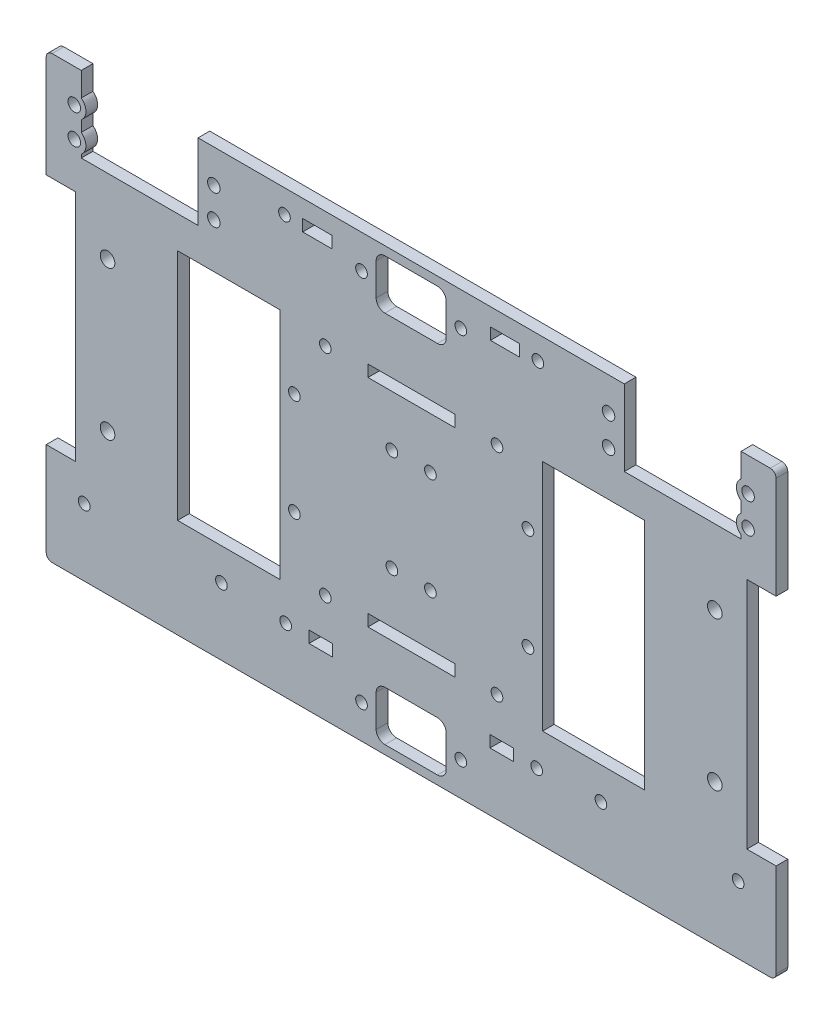
SolidWorks part; units mm, degrees
ref_plane "Front Plane" through (0, 0, 0) normal (0, 0, 1) x (1, 0, 0)
ref_plane "Top Plane" through (0, 0, 0) normal (0, 1, 0) x (1, 0, 0)
ref_plane "Right Plane" through (0, 0, 0) normal (1, 0, 0) x (0, 0, -1)
sketch "Sketch1" plane through (0, 0, 0) normal (0, 0, 1) x (1, 0, 0)
  line L1 (-123, 77) -> (123, 77)
  line L2 (-125, 75) -> (-125, -72)
  line L3 (-123, -74) -> (123, -74)
  line L4 (125, 75) -> (125, -72)
  arc A0 (123, 77) -> (125, 75) centre (123, 75) cw
  arc A1 (-125, 75) -> (-123, 77) centre (-123, 75) cw
  arc A2 (125, -72) -> (123, -74) centre (123, -72) cw
  arc A3 (-125, -72) -> (-123, -74) centre (-123, -72) ccw
  point P7 (125, 77)
  point P10 (-125, 77)
  point P15 (-125, -74)
  dimension "D5" = 2
  dimension "D6" = 2
  dimension "D7" = 2
  dimension "D1" = 250
  dimension "D2" = 151
  dimension "D3" = 74
  dimension "D4" = 125
extrude "Boss-Extrude1" add sketch "Sketch1" along normal blind 4
sketch "Sketch2" plane through (0, 0, 0) normal (0, 0, -1) x (-1, 0, 0)
  line L0 (0, 77) -> (0, -74) construction
  line L4 (-123, 77) -> (123, 77) construction
  line L5 (123, -74) -> (-123, -74) construction
  line L10 (-125, 40) -> (-125, -40)
  line L15 (-115, -40) -> (-125, -40)
  line L16 (-115, 40) -> (-115, -40)
  line L17 (-125, 40) -> (-115, 40)
  line L18 (-45, -40) -> (-80, -40)
  line L19 (-80, -40) -> (-80, 40)
  line L20 (-80, 40) -> (-45, 40)
  line L21 (-45, 40) -> (-45, -40)
  line L22 (125, 40) -> (115, 40)
  line L23 (-125, -72) -> (-125, 75) construction
  line L24 (-192.8803, 0) -> (128.2258, 0) construction
  line L25 (115, 40) -> (115, -40)
  line L26 (115, -40) -> (125, -40)
  line L27 (125, 40) -> (125, -40)
  line L28 (45, 40) -> (45, -40)
  line L29 (80, 40) -> (45, 40)
  line L30 (80, -40) -> (80, 40)
  line L31 (45, -40) -> (80, -40)
  circle A4 centre (-6.6, -17.5) radius 2
  circle A5 centre (-6.6, 17.5) radius 2
  circle A6 centre (-40, -17.5) radius 2
  circle A7 centre (-40, 17.5) radius 2
  circle A8 centre (6.6, 17.5) radius 2
  circle A9 centre (6.6, -17.5) radius 2
  circle A10 centre (40, -17.5) radius 2
  circle A11 centre (40, 17.5) radius 2
  point P24 (-80, 0)
  dimension "D14" = 4
  dimension "D15" = 4
  dimension "D16" = 4
  dimension "D17" = 4
  dimension "D18" = 115
  dimension "D19" = 40
  dimension "D2" = 40
  dimension "D3" = 45
  dimension "D4" = 10
  dimension "D5" = 45
  dimension "D6" = 40
  dimension "D7" = 17.5
  dimension "D8" = 40
  dimension "D9" = 40
  dimension "D10" = 40
  dimension "D11" = 33.4
  dimension "D12" = 33.4
  dimension "D13" = 35
extrude "Cut-Extrude1" cut sketch "Sketch2" against normal blind 10
sketch "Sketch4" plane through (0, 0, 0) normal (0, 0, -1) x (-1, 0, 0)
  line L5 (15, 35) -> (15, 40.2)
  line L7 (-15, 35) -> (-15, 40.2)
  line L9 (-15, -40.2) -> (15, -40.2)
  line L14 (0, 0) -> (-74.7246, 0) construction
  line L15 (15, -35) -> (-15, -35)
  line L16 (0, 0) -> (0, 45.381) construction
  line L20 (15, 35) -> (15, 40.2)
  line L21 (-15, -35) -> (-15, -40.2)
  line L22 (15, -35) -> (15, -40.2)
  line L23 (-15, -35) -> (-15, -40.2)
  line L24 (15, -35) -> (15, -40.2)
  line L25 (-15, 35) -> (-15, 40.2)
  line L26 (15, 35) -> (-15, 35)
  line L27 (-15, 40.2) -> (15, 40.2)
  line L28 (-45, -40) -> (-45, 40) construction
  dimension "D1" = 30
  dimension "D2" = 35
  dimension "D3" = 5.2
  dimension "D4" = 30
extrude "Cut-Extrude3" [suppressed] cut sketch "Sketch4" against normal blind 10 contours L22 L15 L21 L9 | L27 L7 L26 L5
sketch "Sketch6" plane through (0, 0, 0) normal (0, 0, -1) x (-1, 0, 0)
  line L0 (0, 0) -> (-136.3879, 0) construction
  line L1 (0, 0) -> (0, 55.1301) construction
  circle A1 centre (-104, -25.5) radius 2.5
  circle A3 centre (-104, 25.5) radius 2.5
  circle A4 centre (104, -25.5) radius 2.5
  circle A5 centre (104, 25.5) radius 2.5
  dimension "D1" = 5
  dimension "D2" = 5
  dimension "D3" = 25.5
  dimension "D4" = 104
  dimension "D5" = 51
extrude "Cut-Extrude5" cut sketch "Sketch6" against normal blind 10
sketch "Sketch7" plane through (0, 0, 0) normal (0, 0, -1) x (-1, 0, 0)
  line L0 (0, 0) -> (0, -64.9277) construction
  line L1 (0, 0) -> (-69.7221, 0) construction
  circle A0 centre (29.9, 37.5) radius 2
  circle A1 centre (-29.9, -37.5) radius 2
  circle A2 centre (-29.9, 37.5) radius 2
  circle A3 centre (29.9, -37.5) radius 2
  dimension "D3" = 4
  dimension "D5" = 4
  dimension "D1" = 29.9
  dimension "D2" = 37.5
  dimension "D4" = 59.8
extrude "Cut-Extrude6" [suppressed] cut sketch "Sketch7" against normal blind 10 contours A1 | A3 | A2 | A0
sketch "Sketch8" plane through (0, 0, 0) normal (0, 0, -1) x (-1, 0, 0)
  line L0 (0, 0) -> (0, 89.5315) construction
  line L1 (0, 0) -> (69.2283, 0) construction
  line L2 (5.5, 71) -> (-5.5, 71)
  line L3 (-8.5, 68) -> (-8.5, 53)
  line L4 (-5.5, 50) -> (5.5, 50)
  line L5 (8.5, 53) -> (8.5, 68)
  line L6 (-123, 77) -> (123, 77) construction
  arc A0 (-8.5, 68) -> (-5.5, 71) centre (-5.5, 68) cw
  arc A1 (-8.5, 53) -> (-5.5, 50) centre (-5.5, 53) ccw
  arc A2 (5.5, 50) -> (8.5, 53) centre (5.5, 53) ccw
  arc A3 (5.5, 71) -> (8.5, 68) centre (5.5, 68) cw
  dimension "D5" = 3
  dimension "D1" = 6
  dimension "D2" = 8.5
  dimension "D3" = 8.5
  dimension "D4" = 21
extrude "Cut-Extrude7" [suppressed] cut sketch "Sketch8" against normal blind 70
sketch "Sketch10" plane through (0, 0, 0) normal (0, 0, -1) x (-1, 0, 0)
  line L0 (0, 0) -> (59.5887, 0) construction
  line L1 (0, 0) -> (0, 43.3786) construction
  circle A0 centre (13, 60.5) radius 2
  circle A1 centre (-13, 60.5) radius 2
  dimension "D2" = 4
  dimension "D3" = 4
  dimension "D1" = 13
  dimension "D4" = 13
  dimension "D5" = 60.5
extrude "Cut-Extrude8" [suppressed] cut sketch "Sketch10" against normal blind 5
sketch "Sketch11" plane through (0, 0, 0) normal (0, 0, -1) x (-1, 0, 0)
  line L0 (0, 0) -> (0, -54) construction
  line L1 (0, 0) -> (-72.0295, 0) construction
  line L2 (123, -74) -> (-123, -74) construction
  line L3 (-9, -54) -> (9, -54)
  line L4 (-12, -57) -> (-12, -68)
  line L5 (-9, -71) -> (9, -71)
  line L6 (12, -57) -> (12, -68)
  line L8 (-9, 74) -> (9, 74)
  line L9 (-12, 60) -> (-12, 71)
  line L10 (-9, 57) -> (9, 57)
  line L11 (0, 74) -> (0, 57) construction
  line L13 (-123, 77) -> (123, 77) construction
  line L14 (12, 60) -> (12, 71)
  arc A0 (12, -68) -> (9, -71) centre (9, -68) cw
  arc A1 (12, -57) -> (9, -54) centre (9, -57) ccw
  arc A2 (-12, -68) -> (-9, -71) centre (-9, -68) ccw
  arc A3 (-12, -57) -> (-9, -54) centre (-9, -57) cw
  circle A4 centre (-17, -62.5) radius 2
  circle A5 centre (17, -62.5) radius 2
  circle A7 centre (-17, 65.5) radius 2
  arc A8 (-12, 60) -> (-9, 57) centre (-9, 60) ccw
  arc A9 (-12, 71) -> (-9, 74) centre (-9, 71) cw
  arc A10 (12, 71) -> (9, 74) centre (9, 71) ccw
  arc A11 (12, 60) -> (9, 57) centre (9, 60) cw
  circle A12 centre (17, 65.5) radius 2
  dimension "D5" = 3
  dimension "D7" = 4
  dimension "D10" = 4
  dimension "D13" = 3
  dimension "D14" = 3
  dimension "D15" = 9
  dimension "D17" = 3
  dimension "D20" = 4
  dimension "D1" = 12
  dimension "D2" = 12
  dimension "D3" = 17
  dimension "D4" = 20
  dimension "D6" = 11.5
  dimension "D8" = 17
  dimension "D9" = 17
  dimension "D11" = 9
  dimension "D12" = 11
  dimension "D16" = 17
  dimension "D19" = 5.5
  dimension "D24" = 5
extrude "Cut-Extrude9" cut sketch "Sketch11" against normal blind 10
sketch "Sketch16" plane through (0, 0, 0) normal (0, 0, -1) x (-1, 0, 0)
  line L0 (-113, 77) -> (-113, 51)
  line L1 (-123, 77) -> (123, 77) construction
  line L2 (-113, 51) -> (-73, 51)
  line L3 (-73, 51) -> (-73, 77)
  line L5 (0, 0) -> (0, 95.5672) construction
  line L6 (0, 0) -> (-125.0994, 0) construction
  line L7 (-113, 77) -> (-73, 77)
  line L8 (113, 77) -> (73, 77)
  line L9 (73, 51) -> (73, 77)
  line L10 (113, 51) -> (73, 51)
  line L11 (113, 77) -> (113, 51)
  dimension "D1" = 73
  dimension "D3" = 40
  dimension "D4" = 26
extrude "Cut-Extrude10" cut sketch "Sketch16" against normal blind 10
sketch "Sketch17" plane through (0, 0, 0) normal (0, 0, -1) x (-1, 0, 0)
  line L0 (0, 0) -> (-153.5219, 0) construction
  line L1 (0, 0) -> (0, 113.679) construction
  circle A1 centre (67.6, 65.6) radius 2.15
  circle A3 centre (67.6, 55.4) radius 2.15
  circle A5 centre (115.4, 55.4) radius 2.15
  circle A7 centre (115.4, 65.6) radius 2.15
  circle A8 centre (-115.4, 65.6) radius 2.15
  circle A9 centre (-115.4, 55.4) radius 2.15
  circle A10 centre (-67.6, 55.4) radius 2.15
  circle A11 centre (-67.6, 65.6) radius 2.15
  dimension "D1" = 4.3
  dimension "D2" = 4.3
  dimension "D3" = 4.3
  dimension "D4" = 4.3
  dimension "D5" = 65.6
  dimension "D6" = 115.4
  dimension "D7" = 10.2
  dimension "D8" = 47.8
extrude "Cut-Extrude11" cut sketch "Sketch17" against normal blind 10
sketch "Sketch18" plane through (0, 0, 0) normal (0, 0, -1) x (-1, 0, 0)
  line L0 (-73, 77) -> (73, 77) construction
  line L2 (73, 77) -> (73, 51) construction
  line L3 (-73, 51) -> (-73, 77) construction
  circle A0 centre (-43.2, 68.5) radius 2
  circle A2 centre (43.2, 68.5) radius 2
  dimension "D1" = 4
  dimension "D2" = 68.5
  dimension "D3" = 4
  dimension "D4" = 8.5
  dimension "D5" = 29.8
  dimension "D6" = 29.8
extrude "Cut-Extrude12" [suppressed] cut sketch "Sketch18" against normal blind 10
sketch "Sketch19" plane through (0, 0, 0) normal (0, 0, -1) x (-1, 0, 0)
  line L0 (123, -74) -> (-123, -74) construction
  line L1 (0, 0) -> (0, -74) construction
  line L22 (-73, 51) -> (-113, 51)
  line L23 (-73, 77) -> (-73, 51)
  line L24 (73, 77) -> (-73, 77)
  line L25 (73, 51) -> (73, 77)
  line L26 (113, 51) -> (73, 51)
  line L27 (113, 77) -> (113, 51)
  line L28 (123, 77) -> (113, 77)
  line L29 (125, 40) -> (125, 75)
  line L30 (115, 40) -> (125, 40)
  line L31 (115, -40) -> (115, 40)
  line L32 (125, -40) -> (115, -40)
  line L33 (125, -72) -> (125, -40)
  line L34 (-123, -74) -> (123, -74)
  line L35 (-125, -40) -> (-125, -72)
  line L36 (-115, -40) -> (-125, -40)
  line L37 (-115, 40) -> (-115, -40)
  line L38 (-125, 40) -> (-115, 40)
  line L39 (125, -72) -> (125, -40)
  line L40 (-113, 77) -> (-123, 77)
  line L41 (-113, 51) -> (-113, 77)
  line L52 (125, -40) -> (115, -40)
  line L54 (-123, -74) -> (123, -74)
  line L55 (-125, -40) -> (-125, -72)
  line L56 (-115, -40) -> (-125, -40)
  line L57 (-125, 75) -> (-125, 40)
  arc A4 (125, 75) -> (123, 77) centre (123, 75) ccw
  arc A5 (123, -74) -> (125, -72) centre (123, -72) ccw
  arc A6 (-125, -72) -> (-123, -74) centre (-123, -72) ccw
  arc A7 (-123, 77) -> (-125, 75) centre (-123, 75) ccw
  arc A9 (123, -74) -> (125, -72) centre (123, -72) ccw
  arc A10 (-125, -72) -> (-123, -74) centre (-123, -72) ccw
  spline S0 degree 2 poles (-115, -40) (-63.7221, -74) (0, -74) knots 0 0 0 1 1 1
  spline S1 degree 2 poles (115, -40) (63.7221, -74) (0, -74) knots 0 0 0 1 1 1
  point P5 (0, -74)
  dimension "D1" = 0
extrude "Cut-Extrude14" [suppressed] cut sketch "Sketch19" against normal blind 5 contours L52 S1 L54 A9 L39 | S0 L56 L55 A10 L54
sketch "Sketch24" plane through (0, 0, 0) normal (0, 0, -1) x (-1, 0, 0)
  line L5 (0, 0) -> (-23.4044, 0) construction
  line L12 (0, 0) -> (0, -63.755) construction
  circle A0 centre (-42.8, -52.5) radius 2
  circle A2 centre (42.8, -52.5) radius 2
  dimension "D1" = 4
  dimension "D2" = 42.8
  dimension "D3" = 52.5
extrude "Cut-Extrude17" [suppressed] cut sketch "Sketch24" against normal blind 5
sketch "Sketch26" plane through (0, 0, 0) normal (0, 0, -1) x (-1, 0, 0)
  line L0 (0, 0) -> (0, -87.1196) construction
  line L1 (0, 0) -> (-65, 0) construction
  circle A1 centre (-112, -51) radius 2
  circle A3 centre (-65, -51) radius 2
  circle A4 centre (65, -51) radius 2
  circle A5 centre (112, -51) radius 2
  dimension "D2" = 65
  dimension "D3" = 4
  dimension "D4" = 4
  dimension "D1" = 51
  dimension "D5" = 47
extrude "Cut-Extrude18" cut sketch "Sketch26" against normal blind 10
sketch "Sketch28" plane through (0, 0, 0) normal (0, 0, -1) x (-1, 0, 0)
  line L0 (0, 0) -> (0, 91.6279) construction
  circle A0 centre (-115.4, 65.6) radius 2.15
  circle A1 centre (-115.4, 65.6) radius 4
  circle A2 centre (-115.4, 55.4) radius 2.15
  circle A3 centre (-115.4, 55.4) radius 4
  circle A4 centre (115.4, 55.4) radius 4
  circle A5 centre (115.4, 55.4) radius 2.15
  circle A6 centre (115.4, 65.6) radius 4
  circle A7 centre (115.4, 65.6) radius 2.15
  dimension "D1" = 4.3
  dimension "D2" = 8
  dimension "D3" = 4.3
  dimension "D4" = 8
extrude "Boss-Extrude2" add sketch "Sketch28" against normal blind 4
sketch "Sketch29" plane through (0, 0, 4) normal (0, 0, 1) x (1, 0, 0)
  line L24 (-27, -50) -> (-27, -54)
  line L25 (-27, -54) -> (-35, -54)
  line L26 (-35, -50) -> (-35, -54)
  line L27 (-27, -50) -> (-35, -50)
  line L28 (35, -50) -> (35, -54)
  line L29 (35, -54) -> (27, -54)
  line L30 (27, -50) -> (27, -54)
  line L31 (35, -50) -> (27, -50)
  line L32 (15, -35) -> (15, -39)
  line L33 (15, -39) -> (-14.8, -39)
  line L34 (-14.8, -35) -> (-14.8, -39)
  line L35 (15, -35) -> (-14.8, -35)
  line L36 (15, 39) -> (15, 35)
  line L37 (15, 35) -> (-14.8, 35)
  line L38 (-14.8, 39) -> (-14.8, 35)
  line L39 (15, 39) -> (-14.8, 39)
  line L40 (27.15, 71) -> (37.15, 71)
  line L41 (37.15, 67) -> (37.15, 71)
  line L42 (27.15, 67) -> (37.15, 67)
  line L43 (27.15, 67) -> (27.15, 71)
  line L44 (-37.15, 67) -> (-37.15, 71)
  line L45 (-37.15, 67) -> (-27.15, 67)
  line L46 (-27.15, 67) -> (-27.15, 71)
  line L47 (-37.15, 71) -> (-27.15, 71)
extrude "Cut-Extrude19" cut sketch "Sketch29" against normal blind 10
sketch "Sketch30" plane through (0, 0, 0) normal (0, 0, -1) x (-1, 0, 0)
  circle A0 centre (43.4, 69) radius 2
  circle A1 centre (-43.4, 69) radius 2
  circle A2 centre (-29.4, 37) radius 2
  circle A3 centre (29.4, 37) radius 2
  circle A4 centre (29.4, -37) radius 2
  circle A5 centre (-29.4, -37) radius 2
  circle A6 centre (-43, -52) radius 2
  circle A7 centre (43, -52) radius 2
  dimension "D1" = 4
  dimension "D2" = 4
  dimension "D3" = 4
  dimension "D4" = 4
  dimension "D5" = 4
  dimension "D6" = 4
  dimension "D7" = 4
  dimension "D8" = 4
extrude "Cut-Extrude20" cut sketch "Sketch30" against normal blind 10
